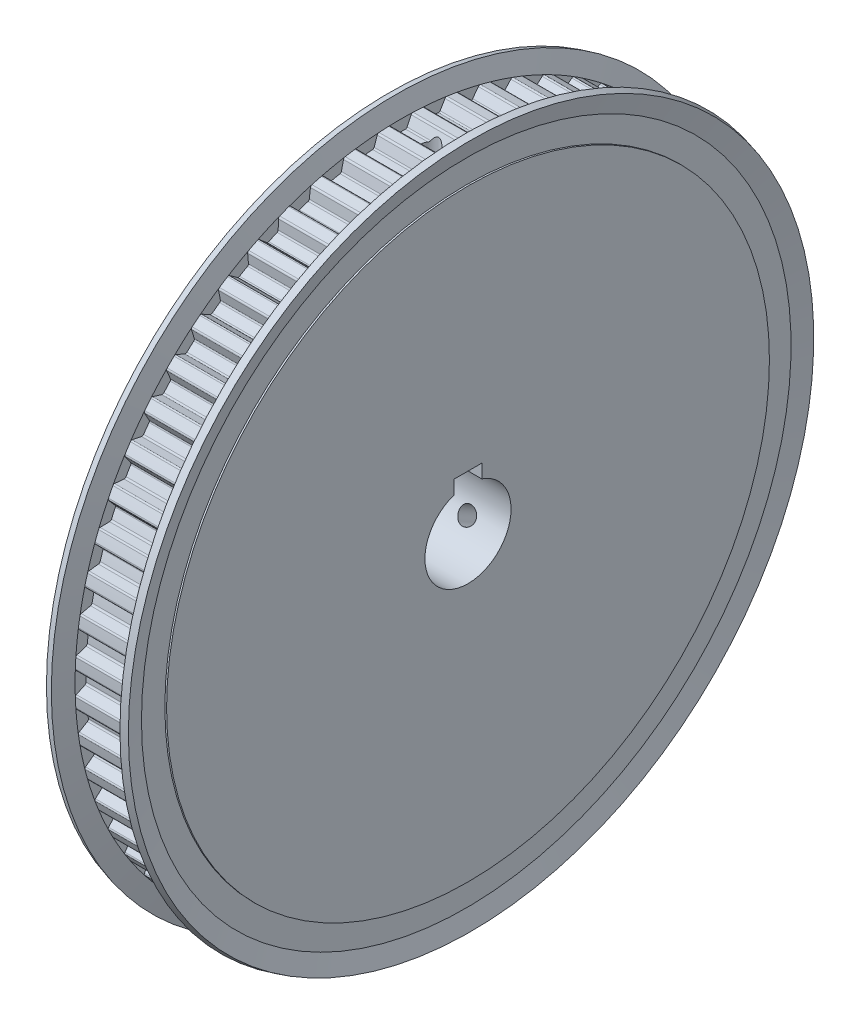
SolidWorks part; units mm, degrees
material "1023 Carbon Steel Sheet (SS)"
ref_plane "Plano frontal" through (0, 0, 0) normal (0, 0, 1) x (1, 0, 0)
ref_plane "Plano superior" through (0, 0, 0) normal (0, 1, 0) x (1, 0, 0)
ref_plane "Plano direito" through (0, 0, 0) normal (1, 0, 0) x (0, 0, -1)
ref_plane "Plane1" through (0, 0, 0) normal (0, 0, 1) x (1, 0, 0)
sketch "Sketch1" plane through (0, 0, 0) normal (0, 0, 1) x (1, 0, 0)
  line L0 (0, 0) -> (0, 87.5)
  line L1 (0, 87.5) -> (0.5, 87.5)
  line L2 (0.5, 87.5) -> (0.5, 94.2867)
  line L3 (0.5, 94.2867) -> (-0.8922, 99.4824)
  line L4 (-0.8922, 99.4824) -> (1.0397, 100)
  line L5 (1.0397, 100) -> (2.5, 94.55)
  line L6 (2.5, 94.55) -> (19.5, 94.55)
  line L7 (19.5, 94.55) -> (20.9603, 100)
  line L8 (20.9603, 100) -> (22.8922, 99.4824)
  line L9 (22.8922, 99.4824) -> (21.5, 94.2867)
  line L10 (21.5, 94.2867) -> (21.5, 87.5)
  line L11 (21.5, 87.5) -> (22, 87.5)
  line L12 (22, 87.5) -> (22, 0)
  line L13 (22, 0) -> (0, 0)
  line L14 (22, 0) -> (0, 0) construction
revolve "Revolve1" add sketch "Sketch1" angle 360 about L14 reverse direction yes
ref_plane "Plane2" through (0, 0, 0) normal (0, 0, 1) x (1, 0, 0)
sketch "Sketch2" plane through (0, 0, 0) normal (0, 0, 1) x (1, 0, 0)
  line L0 (0, 0) -> (0, 12.5)
  line L1 (0, 12.5) -> (22, 12.5)
  line L2 (22, 12.5) -> (22, 0)
  line L3 (22, 0) -> (0, 0)
  line L4 (22, 0) -> (0, 0) construction
revolve "Cut-Revolve1" cut sketch "Sketch2" angle 360 about L4 reverse direction yes
ref_plane "Plane3" through (2.5, 0, 0) normal (1, 0, 0) x (0, 0, -1)
sketch "Sketch3" plane through (2.5, 0, 0) normal (1, 0, 0) x (0, 0, -1)
  line L0 (-3.5415, 95.4293) -> (-3.5065, 94.485)
  line L1 (-3.0348, 94.1966) -> (-1.8645, 91.6869)
  line L2 (1.8371, 91.6283) -> (3.0067, 94.1365)
  line L3 (3.5732, 94.4825) -> (3.6089, 95.4268)
  arc A0 (-3.5065, 94.485) -> (-3.0348, 94.1966) centre (-3.4879, 93.9853) cw
  arc A1 (-1.8645, 91.6869) -> (-1.3121, 91.3406) centre (-1.3207, 91.9405) ccw
  arc A2 (-1.3121, 91.3406) -> (1.3764, 91.3396) centre (0, 0) cw
  arc A3 (1.3764, 91.3396) -> (1.8371, 91.6283) centre (1.384, 91.8396) ccw
  arc A4 (3.0067, 94.1365) -> (3.5732, 94.4825) centre (3.5505, 93.8829) cw
  arc A5 (3.6089, 95.4268) -> (-3.5415, 95.4293) centre (0, 0) ccw
extrude "Cut-Extrude1" cut sketch "Sketch3" along normal blind 17
ref_plane "Plane4" through (2.5, 0, 0) normal (1, 0, 0) x (0, 0, -1)
sketch "Sketch4" plane through (2.5, 0, 0) normal (1, 0, 0) x (0, 0, -1)
  line L0 (6.453, 95.2767) -> (6.3891, 94.3339)
  line L1 (6.8281, 93.9978) -> (7.7296, 91.3796)
  line L2 (11.4048, 90.9343) -> (12.8302, 93.3065)
  line L3 (13.4297, 93.5914) -> (13.5639, 94.5268)
  arc A0 (6.3891, 94.3339) -> (6.8281, 93.9978) centre (6.3553, 93.835) cw
  arc A1 (7.7296, 91.3796) -> (8.2428, 90.9774) centre (8.2969, 91.5749) ccw
  arc A2 (8.2428, 90.9774) -> (10.9165, 90.6954) centre (0, 0) cw
  arc A3 (10.9165, 90.6954) -> (11.4048, 90.9343) centre (10.9762, 91.1918) ccw
  arc A4 (12.8302, 93.3065) -> (13.4297, 93.5914) centre (13.3445, 92.9975) cw
  arc A5 (13.5639, 94.5268) -> (6.453, 95.2767) centre (0, 0) ccw
extrude "Cut-Extrude2" cut sketch "Sketch4" along normal blind 17
ref_plane "Plane5" through (2.5, 0, 0) normal (1, 0, 0) x (0, 0, -1)
sketch "Sketch5" plane through (2.5, 0, 0) normal (1, 0, 0) x (0, 0, -1)
  line L0 (16.3767, 94.0803) -> (16.2147, 93.1493)
  line L1 (16.6161, 92.7692) -> (17.239, 90.071)
  line L2 (20.8476, 89.244) -> (22.5131, 91.4542)
  line L3 (23.1391, 91.6749) -> (23.3704, 92.5911)
  arc A0 (16.2147, 93.1493) -> (16.6161, 92.7692) centre (16.1289, 92.6567) cw
  arc A1 (17.239, 90.071) -> (17.7074, 89.6174) centre (17.8237, 90.206) ccw
  arc A2 (17.7074, 89.6174) -> (20.3369, 89.0575) centre (0, 0) cw
  arc A3 (20.3369, 89.0575) -> (20.8476, 89.244) centre (20.4483, 89.5449) ccw
  arc A4 (22.5131, 91.4542) -> (23.1391, 91.6749) centre (22.9923, 91.0931) cw
  arc A5 (23.3704, 92.5911) -> (16.3767, 94.0803) centre (0, 0) ccw
extrude "Cut-Extrude3" cut sketch "Sketch5" along normal blind 17
ref_plane "Plane6" through (2.5, 0, 0) normal (1, 0, 0) x (0, 0, -1)
sketch "Sketch6" plane through (2.5, 0, 0) normal (1, 0, 0) x (0, 0, -1)
  line L0 (26.1211, 91.8531) -> (25.8626, 90.9441)
  line L1 (26.2221, 90.5241) -> (26.5596, 87.7756)
  line L2 (30.0619, 86.576) -> (31.9493, 88.6)
  line L3 (32.595, 88.754) -> (32.9208, 89.6411)
  arc A0 (25.8626, 90.9441) -> (26.2221, 90.5241) centre (25.7258, 90.4632) cw
  arc A1 (26.5596, 87.7756) -> (26.9779, 87.2755) centre (27.1551, 87.8487) ccw
  arc A2 (26.9779, 87.2755) -> (29.5346, 86.4438) centre (0, 0) cw
  arc A3 (29.5346, 86.4438) -> (30.0619, 86.576) centre (29.6962, 86.917) ccw
  arc A4 (31.9493, 88.6) -> (32.595, 88.754) centre (32.3881, 88.1908) cw
  arc A5 (32.9208, 89.6411) -> (26.1211, 91.8531) centre (0, 0) ccw
extrude "Cut-Extrude4" cut sketch "Sketch6" along normal blind 17
ref_plane "Plane7" through (2.5, 0, 0) normal (1, 0, 0) x (0, 0, -1)
sketch "Sketch7" plane through (2.5, 0, 0) normal (1, 0, 0) x (0, 0, -1)
  line L0 (35.5793, 88.6195) -> (35.2272, 87.7425)
  line L1 (35.5408, 87.2872) -> (35.5891, 84.5185)
  line L2 (38.9469, 82.9594) -> (41.0355, 84.775)
  line L3 (41.6937, 84.8607) -> (42.1105, 85.7088)
  arc A0 (35.2272, 87.7425) -> (35.5408, 87.2872) centre (35.0409, 87.2785) cw
  arc A1 (35.5891, 84.5185) -> (35.9529, 83.9774) centre (36.189, 84.529) ccw
  arc A2 (35.9529, 83.9774) -> (38.4086, 82.8831) centre (0, 0) cw
  arc A3 (38.4086, 82.8831) -> (38.9469, 82.9594) centre (38.6188, 83.3367) ccw
  arc A4 (41.0355, 84.775) -> (41.6937, 84.8607) centre (41.4292, 84.3222) cw
  arc A5 (42.1105, 85.7088) -> (35.5793, 88.6195) centre (0, 0) ccw
extrude "Cut-Extrude5" cut sketch "Sketch7" along normal blind 17
ref_plane "Plane8" through (2.5, 0, 0) normal (1, 0, 0) x (0, 0, -1)
sketch "Sketch8" plane through (2.5, 0, 0) normal (1, 0, 0) x (0, 0, -1)
  line L0 (44.6476, 84.415) -> (44.2058, 83.5796)
  line L1 (44.4701, 83.094) -> (44.2288, 80.3355)
  line L2 (47.4051, 78.4338) -> (49.6721, 80.0212)
  line L3 (50.3357, 80.0376) -> (50.8388, 80.8376)
  arc A0 (44.2058, 83.5796) -> (44.4701, 83.094) centre (43.972, 83.1376) cw
  arc A1 (44.2288, 80.3355) -> (44.534, 79.7593) centre (44.8265, 80.2832) ccw
  arc A2 (44.534, 79.7593) -> (46.8619, 78.4142) centre (0, 0) cw
  arc A3 (46.8619, 78.4142) -> (47.4051, 78.4338) centre (47.1183, 78.8434) ccw
  arc A4 (49.6721, 80.0212) -> (50.3357, 80.0376) centre (50.0163, 79.5297) cw
  arc A5 (50.8388, 80.8376) -> (44.6476, 84.415) centre (0, 0) ccw
extrude "Cut-Extrude6" cut sketch "Sketch8" along normal blind 17
ref_plane "Plane9" through (2.5, 0, 0) normal (1, 0, 0) x (0, 0, -1)
sketch "Sketch9" plane through (2.5, 0, 0) normal (1, 0, 0) x (0, 0, -1)
  line L0 (53.2268, 79.2856) -> (52.7001, 78.501)
  line L1 (52.9122, 77.9905) -> (52.3838, 75.2722)
  line L2 (55.344, 73.049) -> (57.7645, 74.3907)
  line L3 (58.4262, 74.3376) -> (59.0101, 75.0806)
  arc A0 (52.7001, 78.501) -> (52.9122, 77.9905) centre (52.4214, 78.0859) cw
  arc A1 (52.3838, 75.2722) -> (52.6271, 74.6673) centre (52.9728, 75.1577) ccw
  arc A2 (52.6271, 74.6673) -> (54.8017, 73.0863) centre (0, 0) cw
  arc A3 (54.8017, 73.0863) -> (55.344, 73.049) centre (55.1016, 73.4863) ccw
  arc A4 (57.7645, 74.3907) -> (58.4262, 74.3376) centre (58.0554, 73.8659) cw
  arc A5 (59.0101, 75.0806) -> (53.2268, 79.2856) centre (0, 0) ccw
extrude "Cut-Extrude7" cut sketch "Sketch9" along normal blind 17
ref_plane "Plane10" through (2.5, 0, 0) normal (1, 0, 0) x (0, 0, -1)
sketch "Sketch10" plane through (2.5, 0, 0) normal (1, 0, 0) x (0, 0, -1)
  line L0 (61.2228, 73.2875) -> (60.617, 72.5623)
  line L1 (60.7746, 72.0324) -> (59.9649, 69.3843)
  line L2 (62.6765, 66.8638) -> (65.224, 67.9451)
  line L3 (65.8765, 67.8232) -> (66.5349, 68.5011)
  arc A0 (60.617, 72.5623) -> (60.7746, 72.0324) centre (60.2964, 72.1786) cw
  arc A1 (59.9649, 69.3843) -> (60.1437, 68.7572) centre (60.5387, 69.2088) ccw
  arc A2 (60.1437, 68.7572) -> (62.141, 66.9576) centre (0, 0) cw
  arc A3 (62.141, 66.9576) -> (62.6765, 66.8638) centre (62.4812, 67.324) ccw
  arc A4 (65.224, 67.9451) -> (65.8765, 67.8232) centre (65.4585, 67.3928) cw
  arc A5 (66.5349, 68.5011) -> (61.2228, 73.2875) centre (0, 0) ccw
extrude "Cut-Extrude8" cut sketch "Sketch10" along normal blind 17
ref_plane "Plane11" through (2.5, 0, 0) normal (1, 0, 0) x (0, 0, -1)
sketch "Sketch11" plane through (2.5, 0, 0) normal (1, 0, 0) x (0, 0, -1)
  line L0 (68.5481, 66.4865) -> (67.8697, 65.8286)
  line L1 (67.9711, 65.2851) -> (66.8891, 62.7361)
  line L2 (69.3224, 59.946) -> (71.9689, 60.7552)
  line L3 (72.6051, 60.5657) -> (73.3307, 61.171)
  arc A0 (67.8697, 65.8286) -> (67.9711, 65.2851) centre (67.5108, 65.4805) cw
  arc A1 (66.8891, 62.7361) -> (67.0013, 62.0939) centre (67.4414, 62.5017) ccw
  arc A2 (67.0013, 62.0939) -> (68.7996, 60.0952) centre (0, 0) cw
  arc A3 (68.7996, 60.0952) -> (69.3224, 59.946) centre (69.1762, 60.4242) ccw
  arc A4 (71.9689, 60.7552) -> (72.6051, 60.5657) centre (72.1443, 60.1814) cw
  arc A5 (73.3307, 61.171) -> (68.5481, 66.4865) centre (0, 0) ccw
extrude "Cut-Extrude9" cut sketch "Sketch11" along normal blind 17
ref_plane "Plane12" through (2.5, 0, 0) normal (1, 0, 0) x (0, 0, -1)
sketch "Sketch12" plane through (2.5, 0, 0) normal (1, 0, 0) x (0, 0, -1)
  line L0 (75.1223, 58.9571) -> (74.3789, 58.3737)
  line L1 (74.4229, 57.8226) -> (73.0804, 55.4006)
  line L2 (75.2087, 52.3715) -> (77.9253, 52.8995)
  line L3 (78.5382, 52.6446) -> (79.3231, 53.1708)
  arc A0 (74.3789, 58.3737) -> (74.4229, 57.8226) centre (73.9856, 58.065) cw
  arc A1 (73.0804, 55.4006) -> (73.1248, 54.7501) centre (73.6051, 55.1098) ccw
  arc A2 (73.1248, 54.7501) -> (74.7044, 52.5745) centre (0, 0) cw
  arc A3 (74.7044, 52.5745) -> (75.2087, 52.3715) centre (75.1133, 52.8623) ccw
  arc A4 (77.9253, 52.8995) -> (78.5382, 52.6446) centre (78.0398, 52.3106) cw
  arc A5 (79.3231, 53.1708) -> (75.1223, 58.9571) centre (0, 0) ccw
extrude "Cut-Extrude10" cut sketch "Sketch12" along normal blind 17
ref_plane "Plane13" through (2.5, 0, 0) normal (1, 0, 0) x (0, 0, -1)
sketch "Sketch13" plane through (2.5, 0, 0) normal (1, 0, 0) x (0, 0, -1)
  line L0 (80.8734, 50.7817) -> (80.0731, 50.2792)
  line L1 (80.0593, 49.7265) -> (78.471, 47.4582)
  line L2 (80.271, 44.2231) -> (83.0279, 44.4643)
  line L3 (83.6108, 44.1468) -> (84.4465, 44.588)
  arc A0 (80.0731, 50.2792) -> (80.0593, 49.7265) centre (79.6497, 50.0133) cw
  arc A1 (78.471, 47.4582) -> (78.4472, 46.8066) centre (78.9625, 47.114) ccw
  arc A2 (78.4472, 46.8066) -> (79.7907, 44.4778) centre (0, 0) cw
  arc A3 (79.7907, 44.4778) -> (80.271, 44.2231) centre (80.2274, 44.7212) ccw
  arc A4 (83.0279, 44.4643) -> (83.6108, 44.1468) centre (83.0802, 43.8666) cw
  arc A5 (84.4465, 44.588) -> (80.8734, 50.7817) centre (0, 0) ccw
extrude "Cut-Extrude11" cut sketch "Sketch13" along normal blind 17
ref_plane "Plane14" through (2.5, 0, 0) normal (1, 0, 0) x (0, 0, -1)
sketch "Sketch14" plane through (2.5, 0, 0) normal (1, 0, 0) x (0, 0, -1)
  line L0 (85.7385, 42.0499) -> (84.8901, 41.6338)
  line L1 (84.8185, 41.0856) -> (83.0018, 38.9957)
  line L2 (84.4538, 35.5903) -> (87.2209, 35.542)
  line L3 (87.7674, 35.1652) -> (88.6446, 35.5167)
  arc A0 (84.8901, 41.6338) -> (84.8185, 41.0856) centre (84.4412, 41.4136) cw
  arc A1 (83.0018, 38.9957) -> (82.9101, 38.3502) centre (83.4547, 38.6021) ccw
  arc A2 (82.9101, 38.3502) -> (84.0028, 35.8937) centre (0, 0) cw
  arc A3 (84.0028, 35.8937) -> (84.4538, 35.5903) centre (84.4625, 36.0902) ccw
  arc A4 (87.2209, 35.542) -> (87.7674, 35.1652) centre (87.2104, 34.9421) cw
  arc A5 (88.6446, 35.5167) -> (85.7385, 42.0499) centre (0, 0) ccw
extrude "Cut-Extrude12" cut sketch "Sketch14" along normal blind 17
ref_plane "Plane15" through (2.5, 0, 0) normal (1, 0, 0) x (0, 0, -1)
sketch "Sketch15" plane through (2.5, 0, 0) normal (1, 0, 0) x (0, 0, -1)
  line L0 (89.6643, 32.8575) -> (88.777, 32.5323)
  line L1 (88.6485, 31.9946) -> (86.6233, 30.1061)
  line L2 (87.7114, 26.5675) -> (90.4582, 26.2302)
  line L3 (90.9623, 25.7984) -> (91.8715, 26.0562)
  arc A0 (88.777, 32.5323) -> (88.6485, 31.9946) centre (88.3075, 32.3603) cw
  arc A1 (86.6233, 30.1061) -> (86.4646, 29.4737) centre (87.0325, 29.6673) ccw
  arc A2 (86.4646, 29.4737) -> (87.2945, 26.9164) centre (0, 0) cw
  arc A3 (87.2945, 26.9164) -> (87.7114, 26.5675) centre (87.7723, 27.0637) ccw
  arc A4 (90.4582, 26.2302) -> (90.9623, 25.7984) centre (90.3851, 25.6347) cw
  arc A5 (91.8715, 26.0562) -> (89.6643, 32.8575) centre (0, 0) ccw
extrude "Cut-Extrude13" cut sketch "Sketch15" along normal blind 17
ref_plane "Plane16" through (2.5, 0, 0) normal (1, 0, 0) x (0, 0, -1)
sketch "Sketch16" plane through (2.5, 0, 0) normal (1, 0, 0) x (0, 0, -1)
  line L0 (92.6076, 23.305) -> (91.6912, 23.0744)
  line L1 (91.5072, 22.553) -> (89.2957, 20.8865)
  line L2 (90.0079, 17.2536) -> (92.7045, 16.6311)
  line L3 (93.1607, 16.1489) -> (94.0918, 16.3103)
  arc A0 (91.6912, 23.0744) -> (91.5072, 22.553) centre (91.2063, 22.9524) cw
  arc A1 (89.2957, 20.8865) -> (89.0718, 20.2742) centre (89.6568, 20.4074) ccw
  arc A2 (89.0718, 20.2742) -> (89.6298, 17.6442) centre (0, 0) cw
  arc A3 (89.6298, 17.6442) -> (90.0079, 17.2536) centre (90.1204, 17.7408) ccw
  arc A4 (92.7045, 16.6311) -> (93.1607, 16.1489) centre (92.5695, 16.0464) cw
  arc A5 (94.0918, 16.3103) -> (92.6076, 23.305) centre (0, 0) ccw
extrude "Cut-Extrude14" cut sketch "Sketch16" along normal blind 17
ref_plane "Plane17" through (2.5, 0, 0) normal (1, 0, 0) x (0, 0, -1)
sketch "Sketch17" plane through (2.5, 0, 0) normal (1, 0, 0) x (0, 0, -1)
  line L0 (94.5363, 13.4972) -> (93.6008, 13.3636)
  line L1 (93.3634, 12.8644) -> (90.9898, 11.4382)
  line L2 (91.3183, 7.7507) -> (93.9351, 6.8497)
  line L3 (94.3384, 6.3225) -> (95.2813, 6.3857)
  arc A0 (93.6008, 13.3636) -> (93.3634, 12.8644) centre (93.1059, 13.293) cw
  arc A1 (90.9898, 11.4382) -> (90.7031, 10.8526) centre (91.2988, 10.9239) ccw
  arc A2 (90.7031, 10.8526) -> (90.9831, 8.1787) centre (0, 0) cw
  arc A3 (90.9831, 8.1787) -> (91.3183, 7.7507) centre (91.4811, 8.2235) ccw
  arc A4 (93.9351, 6.8497) -> (94.3384, 6.3225) centre (93.7397, 6.2824) cw
  arc A5 (95.2813, 6.3857) -> (94.5363, 13.4972) centre (0, 0) ccw
extrude "Cut-Extrude15" cut sketch "Sketch17" along normal blind 17
ref_plane "Plane18" through (2.5, 0, 0) normal (1, 0, 0) x (0, 0, -1)
sketch "Sketch18" plane through (2.5, 0, 0) normal (1, 0, 0) x (0, 0, -1)
  line L0 (95.4293, 3.5415) -> (94.485, 3.5065)
  line L1 (94.1966, 3.0348) -> (91.6869, 1.8645)
  line L2 (91.6283, -1.8371) -> (94.1365, -3.0067)
  line L3 (94.4825, -3.5732) -> (95.4268, -3.6089)
  arc A0 (94.485, 3.5065) -> (94.1966, 3.0348) centre (93.9853, 3.4879) cw
  arc A1 (91.6869, 1.8645) -> (91.3406, 1.3121) centre (91.9405, 1.3207) ccw
  arc A2 (91.3406, 1.3121) -> (91.3396, -1.3764) centre (0, 0) cw
  arc A3 (91.3396, -1.3764) -> (91.6283, -1.8371) centre (91.8396, -1.384) ccw
  arc A4 (94.1365, -3.0067) -> (94.4825, -3.5732) centre (93.8829, -3.5505) cw
  arc A5 (95.4268, -3.6089) -> (95.4293, 3.5415) centre (0, 0) ccw
extrude "Cut-Extrude16" cut sketch "Sketch18" along normal blind 17
ref_plane "Plane19" through (2.5, 0, 0) normal (1, 0, 0) x (0, 0, -1)
sketch "Sketch19" plane through (2.5, 0, 0) normal (1, 0, 0) x (0, 0, -1)
  line L0 (95.2767, -6.453) -> (94.3339, -6.3891)
  line L1 (93.9978, -6.8281) -> (91.3796, -7.7296)
  line L2 (90.9343, -11.4048) -> (93.3065, -12.8302)
  line L3 (93.5914, -13.4297) -> (94.5268, -13.5639)
  arc A0 (94.3339, -6.3891) -> (93.9978, -6.8281) centre (93.835, -6.3553) cw
  arc A1 (91.3796, -7.7296) -> (90.9774, -8.2428) centre (91.5749, -8.2969) ccw
  arc A2 (90.9774, -8.2428) -> (90.6954, -10.9165) centre (0, 0) cw
  arc A3 (90.6954, -10.9165) -> (90.9343, -11.4048) centre (91.1918, -10.9762) ccw
  arc A4 (93.3065, -12.8302) -> (93.5914, -13.4297) centre (92.9975, -13.3445) cw
  arc A5 (94.5268, -13.5639) -> (95.2767, -6.453) centre (0, 0) ccw
extrude "Cut-Extrude17" cut sketch "Sketch19" along normal blind 17
ref_plane "Plane20" through (2.5, 0, 0) normal (1, 0, 0) x (0, 0, -1)
sketch "Sketch20" plane through (2.5, 0, 0) normal (1, 0, 0) x (0, 0, -1)
  line L0 (94.0803, -16.3767) -> (93.1493, -16.2147)
  line L1 (92.7692, -16.6161) -> (90.071, -17.239)
  line L2 (89.244, -20.8476) -> (91.4542, -22.5131)
  line L3 (91.6749, -23.1391) -> (92.5911, -23.3704)
  arc A0 (93.1493, -16.2147) -> (92.7692, -16.6161) centre (92.6567, -16.1289) cw
  arc A1 (90.071, -17.239) -> (89.6174, -17.7074) centre (90.206, -17.8237) ccw
  arc A2 (89.6174, -17.7074) -> (89.0575, -20.3369) centre (0, 0) cw
  arc A3 (89.0575, -20.3369) -> (89.244, -20.8476) centre (89.5449, -20.4483) ccw
  arc A4 (91.4542, -22.5131) -> (91.6749, -23.1391) centre (91.0931, -22.9923) cw
  arc A5 (92.5911, -23.3704) -> (94.0803, -16.3767) centre (0, 0) ccw
extrude "Cut-Extrude18" cut sketch "Sketch20" along normal blind 17
ref_plane "Plane21" through (2.5, 0, 0) normal (1, 0, 0) x (0, 0, -1)
sketch "Sketch21" plane through (2.5, 0, 0) normal (1, 0, 0) x (0, 0, -1)
  line L0 (91.8531, -26.1211) -> (90.9441, -25.8626)
  line L1 (90.5241, -26.2221) -> (87.7756, -26.5596)
  line L2 (86.576, -30.0619) -> (88.6, -31.9493)
  line L3 (88.754, -32.595) -> (89.6411, -32.9208)
  arc A0 (90.9441, -25.8626) -> (90.5241, -26.2221) centre (90.4632, -25.7258) cw
  arc A1 (87.7756, -26.5596) -> (87.2755, -26.9779) centre (87.8487, -27.1551) ccw
  arc A2 (87.2755, -26.9779) -> (86.4438, -29.5346) centre (0, 0) cw
  arc A3 (86.4438, -29.5346) -> (86.576, -30.0619) centre (86.917, -29.6962) ccw
  arc A4 (88.6, -31.9493) -> (88.754, -32.595) centre (88.1908, -32.3881) cw
  arc A5 (89.6411, -32.9208) -> (91.8531, -26.1211) centre (0, 0) ccw
extrude "Cut-Extrude19" cut sketch "Sketch21" along normal blind 17
ref_plane "Plane22" through (2.5, 0, 0) normal (1, 0, 0) x (0, 0, -1)
sketch "Sketch22" plane through (2.5, 0, 0) normal (1, 0, 0) x (0, 0, -1)
  line L0 (88.6195, -35.5793) -> (87.7425, -35.2272)
  line L1 (87.2872, -35.5408) -> (84.5185, -35.5891)
  line L2 (82.9594, -38.9469) -> (84.775, -41.0355)
  line L3 (84.8607, -41.6937) -> (85.7088, -42.1105)
  arc A0 (87.7425, -35.2272) -> (87.2872, -35.5408) centre (87.2785, -35.0409) cw
  arc A1 (84.5185, -35.5891) -> (83.9774, -35.9529) centre (84.529, -36.189) ccw
  arc A2 (83.9774, -35.9529) -> (82.8831, -38.4086) centre (0, 0) cw
  arc A3 (82.8831, -38.4086) -> (82.9594, -38.9469) centre (83.3367, -38.6188) ccw
  arc A4 (84.775, -41.0355) -> (84.8607, -41.6937) centre (84.3222, -41.4292) cw
  arc A5 (85.7088, -42.1105) -> (88.6195, -35.5793) centre (0, 0) ccw
extrude "Cut-Extrude20" cut sketch "Sketch22" along normal blind 17
ref_plane "Plane23" through (2.5, 0, 0) normal (1, 0, 0) x (0, 0, -1)
sketch "Sketch23" plane through (2.5, 0, 0) normal (1, 0, 0) x (0, 0, -1)
  line L0 (84.415, -44.6476) -> (83.5796, -44.2058)
  line L1 (83.094, -44.4701) -> (80.3355, -44.2288)
  line L2 (78.4338, -47.4051) -> (80.0212, -49.6721)
  line L3 (80.0376, -50.3357) -> (80.8376, -50.8388)
  arc A0 (83.5796, -44.2058) -> (83.094, -44.4701) centre (83.1376, -43.972) cw
  arc A1 (80.3355, -44.2288) -> (79.7593, -44.534) centre (80.2832, -44.8265) ccw
  arc A2 (79.7593, -44.534) -> (78.4142, -46.8619) centre (0, 0) cw
  arc A3 (78.4142, -46.8619) -> (78.4338, -47.4051) centre (78.8434, -47.1183) ccw
  arc A4 (80.0212, -49.6721) -> (80.0376, -50.3357) centre (79.5297, -50.0163) cw
  arc A5 (80.8376, -50.8388) -> (84.415, -44.6476) centre (0, 0) ccw
extrude "Cut-Extrude21" cut sketch "Sketch23" along normal blind 17
ref_plane "Plane24" through (2.5, 0, 0) normal (1, 0, 0) x (0, 0, -1)
sketch "Sketch24" plane through (2.5, 0, 0) normal (1, 0, 0) x (0, 0, -1)
  line L0 (79.2856, -53.2268) -> (78.501, -52.7001)
  line L1 (77.9905, -52.9122) -> (75.2722, -52.3838)
  line L2 (73.049, -55.344) -> (74.3907, -57.7645)
  line L3 (74.3376, -58.4262) -> (75.0806, -59.0101)
  arc A0 (78.501, -52.7001) -> (77.9905, -52.9122) centre (78.0859, -52.4214) cw
  arc A1 (75.2722, -52.3838) -> (74.6673, -52.6271) centre (75.1577, -52.9728) ccw
  arc A2 (74.6673, -52.6271) -> (73.0863, -54.8017) centre (0, 0) cw
  arc A3 (73.0863, -54.8017) -> (73.049, -55.344) centre (73.4863, -55.1016) ccw
  arc A4 (74.3907, -57.7645) -> (74.3376, -58.4262) centre (73.8659, -58.0554) cw
  arc A5 (75.0806, -59.0101) -> (79.2856, -53.2268) centre (0, 0) ccw
extrude "Cut-Extrude22" cut sketch "Sketch24" along normal blind 17
ref_plane "Plane25" through (2.5, 0, 0) normal (1, 0, 0) x (0, 0, -1)
sketch "Sketch25" plane through (2.5, 0, 0) normal (1, 0, 0) x (0, 0, -1)
  line L0 (73.2875, -61.2228) -> (72.5623, -60.617)
  line L1 (72.0324, -60.7746) -> (69.3843, -59.9649)
  line L2 (66.8638, -62.6765) -> (67.9451, -65.224)
  line L3 (67.8232, -65.8765) -> (68.5011, -66.5349)
  arc A0 (72.5623, -60.617) -> (72.0324, -60.7746) centre (72.1786, -60.2964) cw
  arc A1 (69.3843, -59.9649) -> (68.7572, -60.1437) centre (69.2088, -60.5387) ccw
  arc A2 (68.7572, -60.1437) -> (66.9576, -62.141) centre (0, 0) cw
  arc A3 (66.9576, -62.141) -> (66.8638, -62.6765) centre (67.324, -62.4812) ccw
  arc A4 (67.9451, -65.224) -> (67.8232, -65.8765) centre (67.3928, -65.4585) cw
  arc A5 (68.5011, -66.5349) -> (73.2875, -61.2228) centre (0, 0) ccw
extrude "Cut-Extrude23" cut sketch "Sketch25" along normal blind 17
ref_plane "Plane26" through (2.5, 0, 0) normal (1, 0, 0) x (0, 0, -1)
sketch "Sketch26" plane through (2.5, 0, 0) normal (1, 0, 0) x (0, 0, -1)
  line L0 (66.4865, -68.5481) -> (65.8286, -67.8697)
  line L1 (65.2851, -67.9711) -> (62.7361, -66.8891)
  line L2 (59.946, -69.3224) -> (60.7552, -71.9689)
  line L3 (60.5657, -72.6051) -> (61.171, -73.3307)
  arc A0 (65.8286, -67.8697) -> (65.2851, -67.9711) centre (65.4805, -67.5108) cw
  arc A1 (62.7361, -66.8891) -> (62.0939, -67.0013) centre (62.5017, -67.4414) ccw
  arc A2 (62.0939, -67.0013) -> (60.0952, -68.7996) centre (0, 0) cw
  arc A3 (60.0952, -68.7996) -> (59.946, -69.3224) centre (60.4242, -69.1762) ccw
  arc A4 (60.7552, -71.9689) -> (60.5657, -72.6051) centre (60.1814, -72.1443) cw
  arc A5 (61.171, -73.3307) -> (66.4865, -68.5481) centre (0, 0) ccw
extrude "Cut-Extrude24" cut sketch "Sketch26" along normal blind 17
ref_plane "Plane27" through (2.5, 0, 0) normal (1, 0, 0) x (0, 0, -1)
sketch "Sketch27" plane through (2.5, 0, 0) normal (1, 0, 0) x (0, 0, -1)
  line L0 (58.9571, -75.1223) -> (58.3737, -74.3789)
  line L1 (57.8226, -74.4229) -> (55.4006, -73.0804)
  line L2 (52.3715, -75.2087) -> (52.8995, -77.9253)
  line L3 (52.6446, -78.5382) -> (53.1708, -79.3231)
  arc A0 (58.3737, -74.3789) -> (57.8226, -74.4229) centre (58.065, -73.9856) cw
  arc A1 (55.4006, -73.0804) -> (54.7501, -73.1248) centre (55.1098, -73.6051) ccw
  arc A2 (54.7501, -73.1248) -> (52.5745, -74.7044) centre (0, 0) cw
  arc A3 (52.5745, -74.7044) -> (52.3715, -75.2087) centre (52.8623, -75.1133) ccw
  arc A4 (52.8995, -77.9253) -> (52.6446, -78.5382) centre (52.3106, -78.0398) cw
  arc A5 (53.1708, -79.3231) -> (58.9571, -75.1223) centre (0, 0) ccw
extrude "Cut-Extrude25" cut sketch "Sketch27" along normal blind 17
ref_plane "Plane28" through (2.5, 0, 0) normal (1, 0, 0) x (0, 0, -1)
sketch "Sketch28" plane through (2.5, 0, 0) normal (1, 0, 0) x (0, 0, -1)
  line L0 (50.7817, -80.8734) -> (50.2792, -80.0731)
  line L1 (49.7265, -80.0593) -> (47.4582, -78.471)
  line L2 (44.2231, -80.271) -> (44.4643, -83.0279)
  line L3 (44.1468, -83.6108) -> (44.588, -84.4465)
  arc A0 (50.2792, -80.0731) -> (49.7265, -80.0593) centre (50.0133, -79.6497) cw
  arc A1 (47.4582, -78.471) -> (46.8066, -78.4472) centre (47.114, -78.9625) ccw
  arc A2 (46.8066, -78.4472) -> (44.4778, -79.7907) centre (0, 0) cw
  arc A3 (44.4778, -79.7907) -> (44.2231, -80.271) centre (44.7212, -80.2274) ccw
  arc A4 (44.4643, -83.0279) -> (44.1468, -83.6108) centre (43.8666, -83.0802) cw
  arc A5 (44.588, -84.4465) -> (50.7817, -80.8734) centre (0, 0) ccw
extrude "Cut-Extrude26" cut sketch "Sketch28" along normal blind 17
ref_plane "Plane29" through (2.5, 0, 0) normal (1, 0, 0) x (0, 0, -1)
sketch "Sketch29" plane through (2.5, 0, 0) normal (1, 0, 0) x (0, 0, -1)
  line L0 (42.0499, -85.7385) -> (41.6338, -84.8901)
  line L1 (41.0856, -84.8185) -> (38.9957, -83.0018)
  line L2 (35.5903, -84.4538) -> (35.542, -87.2209)
  line L3 (35.1652, -87.7674) -> (35.5167, -88.6446)
  arc A0 (41.6338, -84.8901) -> (41.0856, -84.8185) centre (41.4136, -84.4412) cw
  arc A1 (38.9957, -83.0018) -> (38.3502, -82.9101) centre (38.6021, -83.4547) ccw
  arc A2 (38.3502, -82.9101) -> (35.8937, -84.0028) centre (0, 0) cw
  arc A3 (35.8937, -84.0028) -> (35.5903, -84.4538) centre (36.0902, -84.4625) ccw
  arc A4 (35.542, -87.2209) -> (35.1652, -87.7674) centre (34.9421, -87.2104) cw
  arc A5 (35.5167, -88.6446) -> (42.0499, -85.7385) centre (0, 0) ccw
extrude "Cut-Extrude27" cut sketch "Sketch29" along normal blind 17
ref_plane "Plane30" through (2.5, 0, 0) normal (1, 0, 0) x (0, 0, -1)
sketch "Sketch30" plane through (2.5, 0, 0) normal (1, 0, 0) x (0, 0, -1)
  line L0 (32.8575, -89.6643) -> (32.5323, -88.777)
  line L1 (31.9946, -88.6485) -> (30.1061, -86.6233)
  line L2 (26.5675, -87.7114) -> (26.2302, -90.4582)
  line L3 (25.7984, -90.9623) -> (26.0562, -91.8715)
  arc A0 (32.5323, -88.777) -> (31.9946, -88.6485) centre (32.3603, -88.3075) cw
  arc A1 (30.1061, -86.6233) -> (29.4737, -86.4646) centre (29.6673, -87.0325) ccw
  arc A2 (29.4737, -86.4646) -> (26.9164, -87.2945) centre (0, 0) cw
  arc A3 (26.9164, -87.2945) -> (26.5675, -87.7114) centre (27.0637, -87.7723) ccw
  arc A4 (26.2302, -90.4582) -> (25.7984, -90.9623) centre (25.6347, -90.3851) cw
  arc A5 (26.0562, -91.8715) -> (32.8575, -89.6643) centre (0, 0) ccw
extrude "Cut-Extrude28" cut sketch "Sketch30" along normal blind 17
ref_plane "Plane31" through (2.5, 0, 0) normal (1, 0, 0) x (0, 0, -1)
sketch "Sketch31" plane through (2.5, 0, 0) normal (1, 0, 0) x (0, 0, -1)
  line L0 (23.305, -92.6076) -> (23.0744, -91.6912)
  line L1 (22.553, -91.5072) -> (20.8865, -89.2957)
  line L2 (17.2536, -90.0079) -> (16.6311, -92.7045)
  line L3 (16.1489, -93.1607) -> (16.3103, -94.0918)
  arc A0 (23.0744, -91.6912) -> (22.553, -91.5072) centre (22.9524, -91.2063) cw
  arc A1 (20.8865, -89.2957) -> (20.2742, -89.0718) centre (20.4074, -89.6568) ccw
  arc A2 (20.2742, -89.0718) -> (17.6442, -89.6298) centre (0, 0) cw
  arc A3 (17.6442, -89.6298) -> (17.2536, -90.0079) centre (17.7408, -90.1204) ccw
  arc A4 (16.6311, -92.7045) -> (16.1489, -93.1607) centre (16.0464, -92.5695) cw
  arc A5 (16.3103, -94.0918) -> (23.305, -92.6076) centre (0, 0) ccw
extrude "Cut-Extrude29" cut sketch "Sketch31" along normal blind 17
ref_plane "Plane32" through (2.5, 0, 0) normal (1, 0, 0) x (0, 0, -1)
sketch "Sketch32" plane through (2.5, 0, 0) normal (1, 0, 0) x (0, 0, -1)
  line L0 (13.4972, -94.5363) -> (13.3636, -93.6008)
  line L1 (12.8644, -93.3634) -> (11.4382, -90.9898)
  line L2 (7.7507, -91.3183) -> (6.8497, -93.9351)
  line L3 (6.3225, -94.3384) -> (6.3857, -95.2813)
  arc A0 (13.3636, -93.6008) -> (12.8644, -93.3634) centre (13.293, -93.1059) cw
  arc A1 (11.4382, -90.9898) -> (10.8526, -90.7031) centre (10.9239, -91.2988) ccw
  arc A2 (10.8526, -90.7031) -> (8.1787, -90.9831) centre (0, 0) cw
  arc A3 (8.1787, -90.9831) -> (7.7507, -91.3183) centre (8.2235, -91.4811) ccw
  arc A4 (6.8497, -93.9351) -> (6.3225, -94.3384) centre (6.2824, -93.7397) cw
  arc A5 (6.3857, -95.2813) -> (13.4972, -94.5363) centre (0, 0) ccw
extrude "Cut-Extrude30" cut sketch "Sketch32" along normal blind 17
ref_plane "Plane33" through (2.5, 0, 0) normal (1, 0, 0) x (0, 0, -1)
sketch "Sketch33" plane through (2.5, 0, 0) normal (1, 0, 0) x (0, 0, -1)
  line L0 (3.5415, -95.4293) -> (3.5065, -94.485)
  line L1 (3.0348, -94.1966) -> (1.8645, -91.6869)
  line L2 (-1.8371, -91.6283) -> (-3.0067, -94.1365)
  line L3 (-3.5732, -94.4825) -> (-3.6089, -95.4268)
  arc A0 (3.5065, -94.485) -> (3.0348, -94.1966) centre (3.4879, -93.9853) cw
  arc A1 (1.8645, -91.6869) -> (1.3121, -91.3406) centre (1.3207, -91.9405) ccw
  arc A2 (1.3121, -91.3406) -> (-1.3764, -91.3396) centre (0, 0) cw
  arc A3 (-1.3764, -91.3396) -> (-1.8371, -91.6283) centre (-1.384, -91.8396) ccw
  arc A4 (-3.0067, -94.1365) -> (-3.5732, -94.4825) centre (-3.5505, -93.8829) cw
  arc A5 (-3.6089, -95.4268) -> (3.5415, -95.4293) centre (0, 0) ccw
extrude "Cut-Extrude31" cut sketch "Sketch33" along normal blind 17
ref_plane "Plane34" through (2.5, 0, 0) normal (1, 0, 0) x (0, 0, -1)
sketch "Sketch34" plane through (2.5, 0, 0) normal (1, 0, 0) x (0, 0, -1)
  line L0 (-6.453, -95.2767) -> (-6.3891, -94.3339)
  line L1 (-6.8281, -93.9978) -> (-7.7296, -91.3796)
  line L2 (-11.4048, -90.9343) -> (-12.8302, -93.3065)
  line L3 (-13.4297, -93.5914) -> (-13.5639, -94.5268)
  arc A0 (-6.3891, -94.3339) -> (-6.8281, -93.9978) centre (-6.3553, -93.835) cw
  arc A1 (-7.7296, -91.3796) -> (-8.2428, -90.9774) centre (-8.2969, -91.5749) ccw
  arc A2 (-8.2428, -90.9774) -> (-10.9165, -90.6954) centre (0, 0) cw
  arc A3 (-10.9165, -90.6954) -> (-11.4048, -90.9343) centre (-10.9762, -91.1918) ccw
  arc A4 (-12.8302, -93.3065) -> (-13.4297, -93.5914) centre (-13.3445, -92.9975) cw
  arc A5 (-13.5639, -94.5268) -> (-6.453, -95.2767) centre (0, 0) ccw
extrude "Cut-Extrude32" cut sketch "Sketch34" along normal blind 17
ref_plane "Plane35" through (2.5, 0, 0) normal (1, 0, 0) x (0, 0, -1)
sketch "Sketch35" plane through (2.5, 0, 0) normal (1, 0, 0) x (0, 0, -1)
  line L0 (-16.3767, -94.0803) -> (-16.2147, -93.1493)
  line L1 (-16.6161, -92.7692) -> (-17.239, -90.071)
  line L2 (-20.8476, -89.244) -> (-22.5131, -91.4542)
  line L3 (-23.1391, -91.6749) -> (-23.3704, -92.5911)
  arc A0 (-16.2147, -93.1493) -> (-16.6161, -92.7692) centre (-16.1289, -92.6567) cw
  arc A1 (-17.239, -90.071) -> (-17.7074, -89.6174) centre (-17.8237, -90.206) ccw
  arc A2 (-17.7074, -89.6174) -> (-20.3369, -89.0575) centre (0, 0) cw
  arc A3 (-20.3369, -89.0575) -> (-20.8476, -89.244) centre (-20.4483, -89.5449) ccw
  arc A4 (-22.5131, -91.4542) -> (-23.1391, -91.6749) centre (-22.9923, -91.0931) cw
  arc A5 (-23.3704, -92.5911) -> (-16.3767, -94.0803) centre (0, 0) ccw
extrude "Cut-Extrude33" cut sketch "Sketch35" along normal blind 17
ref_plane "Plane36" through (2.5, 0, 0) normal (1, 0, 0) x (0, 0, -1)
sketch "Sketch36" plane through (2.5, 0, 0) normal (1, 0, 0) x (0, 0, -1)
  line L0 (-26.1211, -91.8531) -> (-25.8626, -90.9441)
  line L1 (-26.2221, -90.5241) -> (-26.5596, -87.7756)
  line L2 (-30.0619, -86.576) -> (-31.9493, -88.6)
  line L3 (-32.595, -88.754) -> (-32.9208, -89.6411)
  arc A0 (-25.8626, -90.9441) -> (-26.2221, -90.5241) centre (-25.7258, -90.4632) cw
  arc A1 (-26.5596, -87.7756) -> (-26.9779, -87.2755) centre (-27.1551, -87.8487) ccw
  arc A2 (-26.9779, -87.2755) -> (-29.5346, -86.4438) centre (0, 0) cw
  arc A3 (-29.5346, -86.4438) -> (-30.0619, -86.576) centre (-29.6962, -86.917) ccw
  arc A4 (-31.9493, -88.6) -> (-32.595, -88.754) centre (-32.3881, -88.1908) cw
  arc A5 (-32.9208, -89.6411) -> (-26.1211, -91.8531) centre (0, 0) ccw
extrude "Cut-Extrude34" cut sketch "Sketch36" along normal blind 17
ref_plane "Plane37" through (2.5, 0, 0) normal (1, 0, 0) x (0, 0, -1)
sketch "Sketch37" plane through (2.5, 0, 0) normal (1, 0, 0) x (0, 0, -1)
  line L0 (-35.5793, -88.6195) -> (-35.2272, -87.7425)
  line L1 (-35.5408, -87.2872) -> (-35.5891, -84.5185)
  line L2 (-38.9469, -82.9594) -> (-41.0355, -84.775)
  line L3 (-41.6937, -84.8607) -> (-42.1105, -85.7088)
  arc A0 (-35.2272, -87.7425) -> (-35.5408, -87.2872) centre (-35.0409, -87.2785) cw
  arc A1 (-35.5891, -84.5185) -> (-35.9529, -83.9774) centre (-36.189, -84.529) ccw
  arc A2 (-35.9529, -83.9774) -> (-38.4086, -82.8831) centre (0, 0) cw
  arc A3 (-38.4086, -82.8831) -> (-38.9469, -82.9594) centre (-38.6188, -83.3367) ccw
  arc A4 (-41.0355, -84.775) -> (-41.6937, -84.8607) centre (-41.4292, -84.3222) cw
  arc A5 (-42.1105, -85.7088) -> (-35.5793, -88.6195) centre (0, 0) ccw
extrude "Cut-Extrude35" cut sketch "Sketch37" along normal blind 17
ref_plane "Plane38" through (2.5, 0, 0) normal (1, 0, 0) x (0, 0, -1)
sketch "Sketch38" plane through (2.5, 0, 0) normal (1, 0, 0) x (0, 0, -1)
  line L0 (-44.6476, -84.415) -> (-44.2058, -83.5796)
  line L1 (-44.4701, -83.094) -> (-44.2288, -80.3355)
  line L2 (-47.4051, -78.4338) -> (-49.6721, -80.0212)
  line L3 (-50.3357, -80.0376) -> (-50.8388, -80.8376)
  arc A0 (-44.2058, -83.5796) -> (-44.4701, -83.094) centre (-43.972, -83.1376) cw
  arc A1 (-44.2288, -80.3355) -> (-44.534, -79.7593) centre (-44.8265, -80.2832) ccw
  arc A2 (-44.534, -79.7593) -> (-46.8619, -78.4142) centre (0, 0) cw
  arc A3 (-46.8619, -78.4142) -> (-47.4051, -78.4338) centre (-47.1183, -78.8434) ccw
  arc A4 (-49.6721, -80.0212) -> (-50.3357, -80.0376) centre (-50.0163, -79.5297) cw
  arc A5 (-50.8388, -80.8376) -> (-44.6476, -84.415) centre (0, 0) ccw
extrude "Cut-Extrude36" cut sketch "Sketch38" along normal blind 17
ref_plane "Plane39" through (2.5, 0, 0) normal (1, 0, 0) x (0, 0, -1)
sketch "Sketch39" plane through (2.5, 0, 0) normal (1, 0, 0) x (0, 0, -1)
  line L0 (-53.2268, -79.2856) -> (-52.7001, -78.501)
  line L1 (-52.9122, -77.9905) -> (-52.3838, -75.2722)
  line L2 (-55.344, -73.049) -> (-57.7645, -74.3907)
  line L3 (-58.4262, -74.3376) -> (-59.0101, -75.0806)
  arc A0 (-52.7001, -78.501) -> (-52.9122, -77.9905) centre (-52.4214, -78.0859) cw
  arc A1 (-52.3838, -75.2722) -> (-52.6271, -74.6673) centre (-52.9728, -75.1577) ccw
  arc A2 (-52.6271, -74.6673) -> (-54.8017, -73.0863) centre (0, 0) cw
  arc A3 (-54.8017, -73.0863) -> (-55.344, -73.049) centre (-55.1016, -73.4863) ccw
  arc A4 (-57.7645, -74.3907) -> (-58.4262, -74.3376) centre (-58.0554, -73.8659) cw
  arc A5 (-59.0101, -75.0806) -> (-53.2268, -79.2856) centre (0, 0) ccw
extrude "Cut-Extrude37" cut sketch "Sketch39" along normal blind 17
ref_plane "Plane40" through (2.5, 0, 0) normal (1, 0, 0) x (0, 0, -1)
sketch "Sketch40" plane through (2.5, 0, 0) normal (1, 0, 0) x (0, 0, -1)
  line L0 (-61.2228, -73.2875) -> (-60.617, -72.5623)
  line L1 (-60.7746, -72.0324) -> (-59.9649, -69.3843)
  line L2 (-62.6765, -66.8638) -> (-65.224, -67.9451)
  line L3 (-65.8765, -67.8232) -> (-66.5349, -68.5011)
  arc A0 (-60.617, -72.5623) -> (-60.7746, -72.0324) centre (-60.2964, -72.1786) cw
  arc A1 (-59.9649, -69.3843) -> (-60.1437, -68.7572) centre (-60.5387, -69.2088) ccw
  arc A2 (-60.1437, -68.7572) -> (-62.141, -66.9576) centre (0, 0) cw
  arc A3 (-62.141, -66.9576) -> (-62.6765, -66.8638) centre (-62.4812, -67.324) ccw
  arc A4 (-65.224, -67.9451) -> (-65.8765, -67.8232) centre (-65.4585, -67.3928) cw
  arc A5 (-66.5349, -68.5011) -> (-61.2228, -73.2875) centre (0, 0) ccw
extrude "Cut-Extrude38" cut sketch "Sketch40" along normal blind 17
ref_plane "Plane41" through (2.5, 0, 0) normal (1, 0, 0) x (0, 0, -1)
sketch "Sketch41" plane through (2.5, 0, 0) normal (1, 0, 0) x (0, 0, -1)
  line L0 (-68.5481, -66.4865) -> (-67.8697, -65.8286)
  line L1 (-67.9711, -65.2851) -> (-66.8891, -62.7361)
  line L2 (-69.3224, -59.946) -> (-71.9689, -60.7552)
  line L3 (-72.6051, -60.5657) -> (-73.3307, -61.171)
  arc A0 (-67.8697, -65.8286) -> (-67.9711, -65.2851) centre (-67.5108, -65.4805) cw
  arc A1 (-66.8891, -62.7361) -> (-67.0013, -62.0939) centre (-67.4414, -62.5017) ccw
  arc A2 (-67.0013, -62.0939) -> (-68.7996, -60.0952) centre (0, 0) cw
  arc A3 (-68.7996, -60.0952) -> (-69.3224, -59.946) centre (-69.1762, -60.4242) ccw
  arc A4 (-71.9689, -60.7552) -> (-72.6051, -60.5657) centre (-72.1443, -60.1814) cw
  arc A5 (-73.3307, -61.171) -> (-68.5481, -66.4865) centre (0, 0) ccw
extrude "Cut-Extrude39" cut sketch "Sketch41" along normal blind 17
ref_plane "Plane42" through (2.5, 0, 0) normal (1, 0, 0) x (0, 0, -1)
sketch "Sketch42" plane through (2.5, 0, 0) normal (1, 0, 0) x (0, 0, -1)
  line L0 (-75.1223, -58.9571) -> (-74.3789, -58.3737)
  line L1 (-74.4229, -57.8226) -> (-73.0804, -55.4006)
  line L2 (-75.2087, -52.3715) -> (-77.9253, -52.8995)
  line L3 (-78.5382, -52.6446) -> (-79.3231, -53.1708)
  arc A0 (-74.3789, -58.3737) -> (-74.4229, -57.8226) centre (-73.9856, -58.065) cw
  arc A1 (-73.0804, -55.4006) -> (-73.1248, -54.7501) centre (-73.6051, -55.1098) ccw
  arc A2 (-73.1248, -54.7501) -> (-74.7044, -52.5745) centre (0, 0) cw
  arc A3 (-74.7044, -52.5745) -> (-75.2087, -52.3715) centre (-75.1133, -52.8623) ccw
  arc A4 (-77.9253, -52.8995) -> (-78.5382, -52.6446) centre (-78.0398, -52.3106) cw
  arc A5 (-79.3231, -53.1708) -> (-75.1223, -58.9571) centre (0, 0) ccw
extrude "Cut-Extrude40" cut sketch "Sketch42" along normal blind 17
ref_plane "Plane43" through (2.5, 0, 0) normal (1, 0, 0) x (0, 0, -1)
sketch "Sketch43" plane through (2.5, 0, 0) normal (1, 0, 0) x (0, 0, -1)
  line L0 (-80.8734, -50.7817) -> (-80.0731, -50.2792)
  line L1 (-80.0593, -49.7265) -> (-78.471, -47.4582)
  line L2 (-80.271, -44.2231) -> (-83.0279, -44.4643)
  line L3 (-83.6108, -44.1468) -> (-84.4465, -44.588)
  arc A0 (-80.0731, -50.2792) -> (-80.0593, -49.7265) centre (-79.6497, -50.0133) cw
  arc A1 (-78.471, -47.4582) -> (-78.4472, -46.8066) centre (-78.9625, -47.114) ccw
  arc A2 (-78.4472, -46.8066) -> (-79.7907, -44.4778) centre (0, 0) cw
  arc A3 (-79.7907, -44.4778) -> (-80.271, -44.2231) centre (-80.2274, -44.7212) ccw
  arc A4 (-83.0279, -44.4643) -> (-83.6108, -44.1468) centre (-83.0802, -43.8666) cw
  arc A5 (-84.4465, -44.588) -> (-80.8734, -50.7817) centre (0, 0) ccw
extrude "Cut-Extrude41" cut sketch "Sketch43" along normal blind 17
ref_plane "Plane44" through (2.5, 0, 0) normal (1, 0, 0) x (0, 0, -1)
sketch "Sketch44" plane through (2.5, 0, 0) normal (1, 0, 0) x (0, 0, -1)
  line L0 (-85.7385, -42.0499) -> (-84.8901, -41.6338)
  line L1 (-84.8185, -41.0856) -> (-83.0018, -38.9957)
  line L2 (-84.4538, -35.5903) -> (-87.2209, -35.542)
  line L3 (-87.7674, -35.1652) -> (-88.6446, -35.5167)
  arc A0 (-84.8901, -41.6338) -> (-84.8185, -41.0856) centre (-84.4412, -41.4136) cw
  arc A1 (-83.0018, -38.9957) -> (-82.9101, -38.3502) centre (-83.4547, -38.6021) ccw
  arc A2 (-82.9101, -38.3502) -> (-84.0028, -35.8937) centre (0, 0) cw
  arc A3 (-84.0028, -35.8937) -> (-84.4538, -35.5903) centre (-84.4625, -36.0902) ccw
  arc A4 (-87.2209, -35.542) -> (-87.7674, -35.1652) centre (-87.2104, -34.9421) cw
  arc A5 (-88.6446, -35.5167) -> (-85.7385, -42.0499) centre (0, 0) ccw
extrude "Cut-Extrude42" cut sketch "Sketch44" along normal blind 17
ref_plane "Plane45" through (2.5, 0, 0) normal (1, 0, 0) x (0, 0, -1)
sketch "Sketch45" plane through (2.5, 0, 0) normal (1, 0, 0) x (0, 0, -1)
  line L0 (-89.6643, -32.8575) -> (-88.777, -32.5323)
  line L1 (-88.6485, -31.9946) -> (-86.6233, -30.1061)
  line L2 (-87.7114, -26.5675) -> (-90.4582, -26.2302)
  line L3 (-90.9623, -25.7984) -> (-91.8715, -26.0562)
  arc A0 (-88.777, -32.5323) -> (-88.6485, -31.9946) centre (-88.3075, -32.3603) cw
  arc A1 (-86.6233, -30.1061) -> (-86.4646, -29.4737) centre (-87.0325, -29.6673) ccw
  arc A2 (-86.4646, -29.4737) -> (-87.2945, -26.9164) centre (0, 0) cw
  arc A3 (-87.2945, -26.9164) -> (-87.7114, -26.5675) centre (-87.7723, -27.0637) ccw
  arc A4 (-90.4582, -26.2302) -> (-90.9623, -25.7984) centre (-90.3851, -25.6347) cw
  arc A5 (-91.8715, -26.0562) -> (-89.6643, -32.8575) centre (0, 0) ccw
extrude "Cut-Extrude43" cut sketch "Sketch45" along normal blind 17
ref_plane "Plane46" through (2.5, 0, 0) normal (1, 0, 0) x (0, 0, -1)
sketch "Sketch46" plane through (2.5, 0, 0) normal (1, 0, 0) x (0, 0, -1)
  line L0 (-92.6076, -23.305) -> (-91.6912, -23.0744)
  line L1 (-91.5072, -22.553) -> (-89.2957, -20.8865)
  line L2 (-90.0079, -17.2536) -> (-92.7045, -16.6311)
  line L3 (-93.1607, -16.1489) -> (-94.0918, -16.3103)
  arc A0 (-91.6912, -23.0744) -> (-91.5072, -22.553) centre (-91.2063, -22.9524) cw
  arc A1 (-89.2957, -20.8865) -> (-89.0718, -20.2742) centre (-89.6568, -20.4074) ccw
  arc A2 (-89.0718, -20.2742) -> (-89.6298, -17.6442) centre (0, 0) cw
  arc A3 (-89.6298, -17.6442) -> (-90.0079, -17.2536) centre (-90.1204, -17.7408) ccw
  arc A4 (-92.7045, -16.6311) -> (-93.1607, -16.1489) centre (-92.5695, -16.0464) cw
  arc A5 (-94.0918, -16.3103) -> (-92.6076, -23.305) centre (0, 0) ccw
extrude "Cut-Extrude44" cut sketch "Sketch46" along normal blind 17
ref_plane "Plane47" through (2.5, 0, 0) normal (1, 0, 0) x (0, 0, -1)
sketch "Sketch47" plane through (2.5, 0, 0) normal (1, 0, 0) x (0, 0, -1)
  line L0 (-94.5363, -13.4972) -> (-93.6008, -13.3636)
  line L1 (-93.3634, -12.8644) -> (-90.9898, -11.4382)
  line L2 (-91.3183, -7.7507) -> (-93.9351, -6.8497)
  line L3 (-94.3384, -6.3225) -> (-95.2813, -6.3857)
  arc A0 (-93.6008, -13.3636) -> (-93.3634, -12.8644) centre (-93.1059, -13.293) cw
  arc A1 (-90.9898, -11.4382) -> (-90.7031, -10.8526) centre (-91.2988, -10.9239) ccw
  arc A2 (-90.7031, -10.8526) -> (-90.9831, -8.1787) centre (0, 0) cw
  arc A3 (-90.9831, -8.1787) -> (-91.3183, -7.7507) centre (-91.4811, -8.2235) ccw
  arc A4 (-93.9351, -6.8497) -> (-94.3384, -6.3225) centre (-93.7397, -6.2824) cw
  arc A5 (-95.2813, -6.3857) -> (-94.5363, -13.4972) centre (0, 0) ccw
extrude "Cut-Extrude45" cut sketch "Sketch47" along normal blind 17
ref_plane "Plane48" through (2.5, 0, 0) normal (1, 0, 0) x (0, 0, -1)
sketch "Sketch48" plane through (2.5, 0, 0) normal (1, 0, 0) x (0, 0, -1)
  line L0 (-95.4293, -3.5415) -> (-94.485, -3.5065)
  line L1 (-94.1966, -3.0348) -> (-91.6869, -1.8645)
  line L2 (-91.6283, 1.8371) -> (-94.1365, 3.0067)
  line L3 (-94.4825, 3.5732) -> (-95.4268, 3.6089)
  arc A0 (-94.485, -3.5065) -> (-94.1966, -3.0348) centre (-93.9853, -3.4879) cw
  arc A1 (-91.6869, -1.8645) -> (-91.3406, -1.3121) centre (-91.9405, -1.3207) ccw
  arc A2 (-91.3406, -1.3121) -> (-91.3396, 1.3764) centre (0, 0) cw
  arc A3 (-91.3396, 1.3764) -> (-91.6283, 1.8371) centre (-91.8396, 1.384) ccw
  arc A4 (-94.1365, 3.0067) -> (-94.4825, 3.5732) centre (-93.8829, 3.5505) cw
  arc A5 (-95.4268, 3.6089) -> (-95.4293, -3.5415) centre (0, 0) ccw
extrude "Cut-Extrude46" cut sketch "Sketch48" along normal blind 17
ref_plane "Plane49" through (2.5, 0, 0) normal (1, 0, 0) x (0, 0, -1)
sketch "Sketch49" plane through (2.5, 0, 0) normal (1, 0, 0) x (0, 0, -1)
  line L0 (-95.2767, 6.453) -> (-94.3339, 6.3891)
  line L1 (-93.9978, 6.8281) -> (-91.3796, 7.7296)
  line L2 (-90.9343, 11.4048) -> (-93.3065, 12.8302)
  line L3 (-93.5914, 13.4297) -> (-94.5268, 13.5639)
  arc A0 (-94.3339, 6.3891) -> (-93.9978, 6.8281) centre (-93.835, 6.3553) cw
  arc A1 (-91.3796, 7.7296) -> (-90.9774, 8.2428) centre (-91.5749, 8.2969) ccw
  arc A2 (-90.9774, 8.2428) -> (-90.6954, 10.9165) centre (0, 0) cw
  arc A3 (-90.6954, 10.9165) -> (-90.9343, 11.4048) centre (-91.1918, 10.9762) ccw
  arc A4 (-93.3065, 12.8302) -> (-93.5914, 13.4297) centre (-92.9975, 13.3445) cw
  arc A5 (-94.5268, 13.5639) -> (-95.2767, 6.453) centre (0, 0) ccw
extrude "Cut-Extrude47" cut sketch "Sketch49" along normal blind 17
ref_plane "Plane50" through (2.5, 0, 0) normal (1, 0, 0) x (0, 0, -1)
sketch "Sketch50" plane through (2.5, 0, 0) normal (1, 0, 0) x (0, 0, -1)
  line L0 (-94.0803, 16.3767) -> (-93.1493, 16.2147)
  line L1 (-92.7692, 16.6161) -> (-90.071, 17.239)
  line L2 (-89.244, 20.8476) -> (-91.4542, 22.5131)
  line L3 (-91.6749, 23.1391) -> (-92.5911, 23.3704)
  arc A0 (-93.1493, 16.2147) -> (-92.7692, 16.6161) centre (-92.6567, 16.1289) cw
  arc A1 (-90.071, 17.239) -> (-89.6174, 17.7074) centre (-90.206, 17.8237) ccw
  arc A2 (-89.6174, 17.7074) -> (-89.0575, 20.3369) centre (0, 0) cw
  arc A3 (-89.0575, 20.3369) -> (-89.244, 20.8476) centre (-89.5449, 20.4483) ccw
  arc A4 (-91.4542, 22.5131) -> (-91.6749, 23.1391) centre (-91.0931, 22.9923) cw
  arc A5 (-92.5911, 23.3704) -> (-94.0803, 16.3767) centre (0, 0) ccw
extrude "Cut-Extrude48" cut sketch "Sketch50" along normal blind 17
ref_plane "Plane51" through (2.5, 0, 0) normal (1, 0, 0) x (0, 0, -1)
sketch "Sketch51" plane through (2.5, 0, 0) normal (1, 0, 0) x (0, 0, -1)
  line L0 (-91.8531, 26.1211) -> (-90.9441, 25.8626)
  line L1 (-90.5241, 26.2221) -> (-87.7756, 26.5596)
  line L2 (-86.576, 30.0619) -> (-88.6, 31.9493)
  line L3 (-88.754, 32.595) -> (-89.6411, 32.9208)
  arc A0 (-90.9441, 25.8626) -> (-90.5241, 26.2221) centre (-90.4632, 25.7258) cw
  arc A1 (-87.7756, 26.5596) -> (-87.2755, 26.9779) centre (-87.8487, 27.1551) ccw
  arc A2 (-87.2755, 26.9779) -> (-86.4438, 29.5346) centre (0, 0) cw
  arc A3 (-86.4438, 29.5346) -> (-86.576, 30.0619) centre (-86.917, 29.6962) ccw
  arc A4 (-88.6, 31.9493) -> (-88.754, 32.595) centre (-88.1908, 32.3881) cw
  arc A5 (-89.6411, 32.9208) -> (-91.8531, 26.1211) centre (0, 0) ccw
extrude "Cut-Extrude49" cut sketch "Sketch51" along normal blind 17
ref_plane "Plane52" through (2.5, 0, 0) normal (1, 0, 0) x (0, 0, -1)
sketch "Sketch52" plane through (2.5, 0, 0) normal (1, 0, 0) x (0, 0, -1)
  line L0 (-88.6195, 35.5793) -> (-87.7425, 35.2272)
  line L1 (-87.2872, 35.5408) -> (-84.5185, 35.5891)
  line L2 (-82.9594, 38.9469) -> (-84.775, 41.0355)
  line L3 (-84.8607, 41.6937) -> (-85.7088, 42.1105)
  arc A0 (-87.7425, 35.2272) -> (-87.2872, 35.5408) centre (-87.2785, 35.0409) cw
  arc A1 (-84.5185, 35.5891) -> (-83.9774, 35.9529) centre (-84.529, 36.189) ccw
  arc A2 (-83.9774, 35.9529) -> (-82.8831, 38.4086) centre (0, 0) cw
  arc A3 (-82.8831, 38.4086) -> (-82.9594, 38.9469) centre (-83.3367, 38.6188) ccw
  arc A4 (-84.775, 41.0355) -> (-84.8607, 41.6937) centre (-84.3222, 41.4292) cw
  arc A5 (-85.7088, 42.1105) -> (-88.6195, 35.5793) centre (0, 0) ccw
extrude "Cut-Extrude50" cut sketch "Sketch52" along normal blind 17
ref_plane "Plane53" through (2.5, 0, 0) normal (1, 0, 0) x (0, 0, -1)
sketch "Sketch53" plane through (2.5, 0, 0) normal (1, 0, 0) x (0, 0, -1)
  line L0 (-84.415, 44.6476) -> (-83.5796, 44.2058)
  line L1 (-83.094, 44.4701) -> (-80.3355, 44.2288)
  line L2 (-78.4338, 47.4051) -> (-80.0212, 49.6721)
  line L3 (-80.0376, 50.3357) -> (-80.8376, 50.8388)
  arc A0 (-83.5796, 44.2058) -> (-83.094, 44.4701) centre (-83.1376, 43.972) cw
  arc A1 (-80.3355, 44.2288) -> (-79.7593, 44.534) centre (-80.2832, 44.8265) ccw
  arc A2 (-79.7593, 44.534) -> (-78.4142, 46.8619) centre (0, 0) cw
  arc A3 (-78.4142, 46.8619) -> (-78.4338, 47.4051) centre (-78.8434, 47.1183) ccw
  arc A4 (-80.0212, 49.6721) -> (-80.0376, 50.3357) centre (-79.5297, 50.0163) cw
  arc A5 (-80.8376, 50.8388) -> (-84.415, 44.6476) centre (0, 0) ccw
extrude "Cut-Extrude51" cut sketch "Sketch53" along normal blind 17
ref_plane "Plane54" through (2.5, 0, 0) normal (1, 0, 0) x (0, 0, -1)
sketch "Sketch54" plane through (2.5, 0, 0) normal (1, 0, 0) x (0, 0, -1)
  line L0 (-79.2856, 53.2268) -> (-78.501, 52.7001)
  line L1 (-77.9905, 52.9122) -> (-75.2722, 52.3838)
  line L2 (-73.049, 55.344) -> (-74.3907, 57.7645)
  line L3 (-74.3376, 58.4262) -> (-75.0806, 59.0101)
  arc A0 (-78.501, 52.7001) -> (-77.9905, 52.9122) centre (-78.0859, 52.4214) cw
  arc A1 (-75.2722, 52.3838) -> (-74.6673, 52.6271) centre (-75.1577, 52.9728) ccw
  arc A2 (-74.6673, 52.6271) -> (-73.0863, 54.8017) centre (0, 0) cw
  arc A3 (-73.0863, 54.8017) -> (-73.049, 55.344) centre (-73.4863, 55.1016) ccw
  arc A4 (-74.3907, 57.7645) -> (-74.3376, 58.4262) centre (-73.8659, 58.0554) cw
  arc A5 (-75.0806, 59.0101) -> (-79.2856, 53.2268) centre (0, 0) ccw
extrude "Cut-Extrude52" cut sketch "Sketch54" along normal blind 17
ref_plane "Plane55" through (2.5, 0, 0) normal (1, 0, 0) x (0, 0, -1)
sketch "Sketch55" plane through (2.5, 0, 0) normal (1, 0, 0) x (0, 0, -1)
  line L0 (-73.2875, 61.2228) -> (-72.5623, 60.617)
  line L1 (-72.0324, 60.7746) -> (-69.3843, 59.9649)
  line L2 (-66.8638, 62.6765) -> (-67.9451, 65.224)
  line L3 (-67.8232, 65.8765) -> (-68.5011, 66.5349)
  arc A0 (-72.5623, 60.617) -> (-72.0324, 60.7746) centre (-72.1786, 60.2964) cw
  arc A1 (-69.3843, 59.9649) -> (-68.7572, 60.1437) centre (-69.2088, 60.5387) ccw
  arc A2 (-68.7572, 60.1437) -> (-66.9576, 62.141) centre (0, 0) cw
  arc A3 (-66.9576, 62.141) -> (-66.8638, 62.6765) centre (-67.324, 62.4812) ccw
  arc A4 (-67.9451, 65.224) -> (-67.8232, 65.8765) centre (-67.3928, 65.4585) cw
  arc A5 (-68.5011, 66.5349) -> (-73.2875, 61.2228) centre (0, 0) ccw
extrude "Cut-Extrude53" cut sketch "Sketch55" along normal blind 17
ref_plane "Plane56" through (2.5, 0, 0) normal (1, 0, 0) x (0, 0, -1)
sketch "Sketch56" plane through (2.5, 0, 0) normal (1, 0, 0) x (0, 0, -1)
  line L0 (-66.4865, 68.5481) -> (-65.8286, 67.8697)
  line L1 (-65.2851, 67.9711) -> (-62.7361, 66.8891)
  line L2 (-59.946, 69.3224) -> (-60.7552, 71.9689)
  line L3 (-60.5657, 72.6051) -> (-61.171, 73.3307)
  arc A0 (-65.8286, 67.8697) -> (-65.2851, 67.9711) centre (-65.4805, 67.5108) cw
  arc A1 (-62.7361, 66.8891) -> (-62.0939, 67.0013) centre (-62.5017, 67.4414) ccw
  arc A2 (-62.0939, 67.0013) -> (-60.0952, 68.7996) centre (0, 0) cw
  arc A3 (-60.0952, 68.7996) -> (-59.946, 69.3224) centre (-60.4242, 69.1762) ccw
  arc A4 (-60.7552, 71.9689) -> (-60.5657, 72.6051) centre (-60.1814, 72.1443) cw
  arc A5 (-61.171, 73.3307) -> (-66.4865, 68.5481) centre (0, 0) ccw
extrude "Cut-Extrude54" cut sketch "Sketch56" along normal blind 17
ref_plane "Plane57" through (2.5, 0, 0) normal (1, 0, 0) x (0, 0, -1)
sketch "Sketch57" plane through (2.5, 0, 0) normal (1, 0, 0) x (0, 0, -1)
  line L0 (-58.9571, 75.1223) -> (-58.3737, 74.3789)
  line L1 (-57.8226, 74.4229) -> (-55.4006, 73.0804)
  line L2 (-52.3715, 75.2087) -> (-52.8995, 77.9253)
  line L3 (-52.6446, 78.5382) -> (-53.1708, 79.3231)
  arc A0 (-58.3737, 74.3789) -> (-57.8226, 74.4229) centre (-58.065, 73.9856) cw
  arc A1 (-55.4006, 73.0804) -> (-54.7501, 73.1248) centre (-55.1098, 73.6051) ccw
  arc A2 (-54.7501, 73.1248) -> (-52.5745, 74.7044) centre (0, 0) cw
  arc A3 (-52.5745, 74.7044) -> (-52.3715, 75.2087) centre (-52.8623, 75.1133) ccw
  arc A4 (-52.8995, 77.9253) -> (-52.6446, 78.5382) centre (-52.3106, 78.0398) cw
  arc A5 (-53.1708, 79.3231) -> (-58.9571, 75.1223) centre (0, 0) ccw
extrude "Cut-Extrude55" cut sketch "Sketch57" along normal blind 17
ref_plane "Plane58" through (2.5, 0, 0) normal (1, 0, 0) x (0, 0, -1)
sketch "Sketch58" plane through (2.5, 0, 0) normal (1, 0, 0) x (0, 0, -1)
  line L0 (-50.7817, 80.8734) -> (-50.2792, 80.0731)
  line L1 (-49.7265, 80.0593) -> (-47.4582, 78.471)
  line L2 (-44.2231, 80.271) -> (-44.4643, 83.0279)
  line L3 (-44.1468, 83.6108) -> (-44.588, 84.4465)
  arc A0 (-50.2792, 80.0731) -> (-49.7265, 80.0593) centre (-50.0133, 79.6497) cw
  arc A1 (-47.4582, 78.471) -> (-46.8066, 78.4472) centre (-47.114, 78.9625) ccw
  arc A2 (-46.8066, 78.4472) -> (-44.4778, 79.7907) centre (0, 0) cw
  arc A3 (-44.4778, 79.7907) -> (-44.2231, 80.271) centre (-44.7212, 80.2274) ccw
  arc A4 (-44.4643, 83.0279) -> (-44.1468, 83.6108) centre (-43.8666, 83.0802) cw
  arc A5 (-44.588, 84.4465) -> (-50.7817, 80.8734) centre (0, 0) ccw
extrude "Cut-Extrude56" cut sketch "Sketch58" along normal blind 17
ref_plane "Plane59" through (2.5, 0, 0) normal (1, 0, 0) x (0, 0, -1)
sketch "Sketch59" plane through (2.5, 0, 0) normal (1, 0, 0) x (0, 0, -1)
  line L0 (-42.0499, 85.7385) -> (-41.6338, 84.8901)
  line L1 (-41.0856, 84.8185) -> (-38.9957, 83.0018)
  line L2 (-35.5903, 84.4538) -> (-35.542, 87.2209)
  line L3 (-35.1652, 87.7674) -> (-35.5167, 88.6446)
  arc A0 (-41.6338, 84.8901) -> (-41.0856, 84.8185) centre (-41.4136, 84.4412) cw
  arc A1 (-38.9957, 83.0018) -> (-38.3502, 82.9101) centre (-38.6021, 83.4547) ccw
  arc A2 (-38.3502, 82.9101) -> (-35.8937, 84.0028) centre (0, 0) cw
  arc A3 (-35.8937, 84.0028) -> (-35.5903, 84.4538) centre (-36.0902, 84.4625) ccw
  arc A4 (-35.542, 87.2209) -> (-35.1652, 87.7674) centre (-34.9421, 87.2104) cw
  arc A5 (-35.5167, 88.6446) -> (-42.0499, 85.7385) centre (0, 0) ccw
extrude "Cut-Extrude57" cut sketch "Sketch59" along normal blind 17
ref_plane "Plane60" through (2.5, 0, 0) normal (1, 0, 0) x (0, 0, -1)
sketch "Sketch60" plane through (2.5, 0, 0) normal (1, 0, 0) x (0, 0, -1)
  line L0 (-32.8575, 89.6643) -> (-32.5323, 88.777)
  line L1 (-31.9946, 88.6485) -> (-30.1061, 86.6233)
  line L2 (-26.5675, 87.7114) -> (-26.2302, 90.4582)
  line L3 (-25.7984, 90.9623) -> (-26.0562, 91.8715)
  arc A0 (-32.5323, 88.777) -> (-31.9946, 88.6485) centre (-32.3603, 88.3075) cw
  arc A1 (-30.1061, 86.6233) -> (-29.4737, 86.4646) centre (-29.6673, 87.0325) ccw
  arc A2 (-29.4737, 86.4646) -> (-26.9164, 87.2945) centre (0, 0) cw
  arc A3 (-26.9164, 87.2945) -> (-26.5675, 87.7114) centre (-27.0637, 87.7723) ccw
  arc A4 (-26.2302, 90.4582) -> (-25.7984, 90.9623) centre (-25.6347, 90.3851) cw
  arc A5 (-26.0562, 91.8715) -> (-32.8575, 89.6643) centre (0, 0) ccw
extrude "Cut-Extrude58" cut sketch "Sketch60" along normal blind 17
ref_plane "Plane61" through (2.5, 0, 0) normal (1, 0, 0) x (0, 0, -1)
sketch "Sketch61" plane through (2.5, 0, 0) normal (1, 0, 0) x (0, 0, -1)
  line L0 (-23.305, 92.6076) -> (-23.0744, 91.6912)
  line L1 (-22.553, 91.5072) -> (-20.8865, 89.2957)
  line L2 (-17.2536, 90.0079) -> (-16.6311, 92.7045)
  line L3 (-16.1489, 93.1607) -> (-16.3103, 94.0918)
  arc A0 (-23.0744, 91.6912) -> (-22.553, 91.5072) centre (-22.9524, 91.2063) cw
  arc A1 (-20.8865, 89.2957) -> (-20.2742, 89.0718) centre (-20.4074, 89.6568) ccw
  arc A2 (-20.2742, 89.0718) -> (-17.6442, 89.6298) centre (0, 0) cw
  arc A3 (-17.6442, 89.6298) -> (-17.2536, 90.0079) centre (-17.7408, 90.1204) ccw
  arc A4 (-16.6311, 92.7045) -> (-16.1489, 93.1607) centre (-16.0464, 92.5695) cw
  arc A5 (-16.3103, 94.0918) -> (-23.305, 92.6076) centre (0, 0) ccw
extrude "Cut-Extrude59" cut sketch "Sketch61" along normal blind 17
ref_plane "Plane62" through (2.5, 0, 0) normal (1, 0, 0) x (0, 0, -1)
sketch "Sketch62" plane through (2.5, 0, 0) normal (1, 0, 0) x (0, 0, -1)
  line L0 (-13.4972, 94.5363) -> (-13.3636, 93.6008)
  line L1 (-12.8644, 93.3634) -> (-11.4382, 90.9898)
  line L2 (-7.7507, 91.3183) -> (-6.8497, 93.9351)
  line L3 (-6.3225, 94.3384) -> (-6.3857, 95.2813)
  arc A0 (-13.3636, 93.6008) -> (-12.8644, 93.3634) centre (-13.293, 93.1059) cw
  arc A1 (-11.4382, 90.9898) -> (-10.8526, 90.7031) centre (-10.9239, 91.2988) ccw
  arc A2 (-10.8526, 90.7031) -> (-8.1787, 90.9831) centre (0, 0) cw
  arc A3 (-8.1787, 90.9831) -> (-7.7507, 91.3183) centre (-8.2235, 91.4811) ccw
  arc A4 (-6.8497, 93.9351) -> (-6.3225, 94.3384) centre (-6.2824, 93.7397) cw
  arc A5 (-6.3857, 95.2813) -> (-13.4972, 94.5363) centre (0, 0) ccw
extrude "Cut-Extrude60" cut sketch "Sketch62" along normal blind 17
ref_plane "Plane63" through (0, 0, 0) normal (1, 0, 0) x (0, 0, -1)
sketch "Sketch63" plane through (0, 0, 0) normal (1, 0, 0) x (0, 0, -1)
  line L0 (-4, 0) -> (4, 0)
  line L1 (4, 0) -> (4, 15.8)
  line L2 (4, 15.8) -> (-4, 15.8)
  line L3 (-4, 15.8) -> (-4, 0)
extrude "Cut-Extrude61" cut sketch "Sketch63" along normal blind 22
ref_plane "Plane64" through (11, 0, 0) normal (1, 0, 0) x (0, 0, -1)
sketch "Sketch64" plane through (11, 0, 0) normal (1, 0, 0) x (0, 0, -1)
  line L0 (0, 94.55) -> (2.4585, 94.55)
  line L1 (2.4585, 94.55) -> (2.4585, 0)
  line L2 (2.4585, 0) -> (0, 0)
  line L3 (0, 0) -> (0, 94.55)
  line L4 (0, 0) -> (0, 94.55) construction
revolve "Cut-Revolve2" cut sketch "Sketch64" angle 360 about L4 reverse direction yes
ref_plane "Plane65" through (11, 0, 0) normal (1, 0, 0) x (0, 0, -1)
sketch "Sketch65" plane through (11, 0, 0) normal (1, 0, 0) x (0, 0, -1)
  line L0 (81.8827, -47.275) -> (80.6535, -49.4041)
  line L1 (80.6535, -49.4041) -> (-1.2293, -2.1291)
  line L2 (-1.2293, -2.1291) -> (0, 0)
  line L3 (0, 0) -> (81.8827, -47.275)
  line L4 (0, 0) -> (81.8827, -47.275) construction
revolve "Cut-Revolve3" cut sketch "Sketch65" angle 360 about L4 reverse direction yes
ref_point "Point1"
ref_point "Point2"
